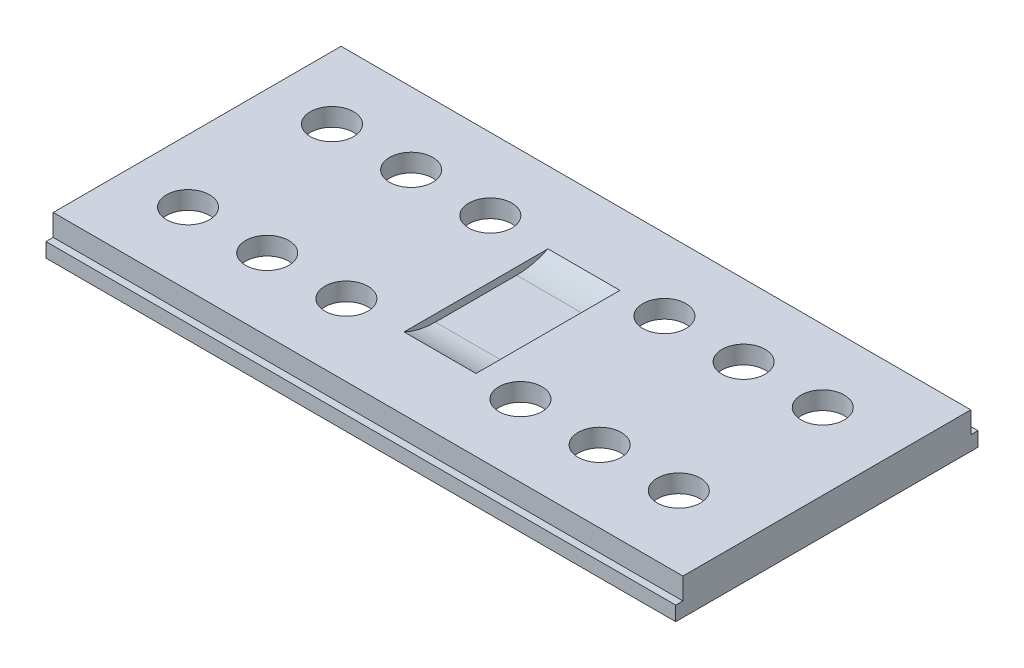
SolidWorks part; units mm, degrees
ref_plane "Front Plane" through (0, 0, 0) normal (0, 0, 1) x (1, 0, 0)
ref_plane "Top Plane" through (0, 0, 0) normal (0, 1, 0) x (1, 0, 0)
ref_plane "Right Plane" through (0, 0, 0) normal (1, 0, 0) x (0, 0, -1)
sketch "Sketch1" plane through (0, 0, 0) normal (0, 1, 0) x (1, 0, 0)
  line L1 (-43.75, 21) -> (43.75, 21)
  line L2 (-43.75, 21) -> (-43.75, -21)
  line L3 (-43.75, -21) -> (43.75, -21)
  line L4 (43.75, 21) -> (43.75, -21)
  line L5 (-43.75, 21) -> (43.75, -21) construction
  line L6 (-43.75, -21) -> (43.75, 21) construction
  point P0 (0, 0)
extrude "Boss-Extrude1" add sketch "Sketch1" along normal blind 5
sketch "Sketch2" plane through (0, 5, 0) normal (0, 1, 0) x (1, 0, 0)
  line L0 (-43.75, 21) -> (-43.75, -21) construction
  line L1 (43.75, 21) -> (-43.75, 21)
  line L2 (43.75, 21) -> (43.75, 20)
  line L3 (43.75, 20) -> (-43.75, 20)
  line L4 (-43.75, 21) -> (-43.75, 20)
  point P7 (0, 0)
extrude "Cut-Extrude1" cut sketch "Sketch2" against normal blind 3
sketch "Sketch3" plane through (0, 5, 0) normal (0, 1, 0) x (1, 0, 0)
  line L0 (43.75, -21) -> (43.75, 20) construction
  line L1 (-43.75, -21) -> (43.75, -21)
  line L2 (-43.75, -21) -> (-43.75, -20)
  line L3 (-43.75, -20) -> (43.75, -20)
  line L4 (43.75, -21) -> (43.75, -20)
extrude "Cut-Extrude2" cut sketch "Sketch3" against normal blind 3
sketch "Sketch4" plane through (0, 5, 0) normal (0, 1, 0) x (1, 0, 0)
  line L1 (-5, 10) -> (5, 10)
  line L2 (-5, 10) -> (-5, -10)
  line L3 (-5, -10) -> (5, -10)
  line L4 (5, 10) -> (5, -10)
  line L5 (-5, 10) -> (5, -10) construction
  line L6 (-5, -10) -> (5, 10) construction
  point P0 (0, 0)
extrude "Cut-Extrude3" cut sketch "Sketch4" against normal blind 1
fillet "Fillet1" radius 10 1 edges at (0, 4, 10)
fillet "Fillet2" radius 10 1 edges at (0, 4, -10)
shell "Shell6" thickness 2.5 removed face at (0, 0, 0)
sketch "Sketch5" plane through (0, 5, 0) normal (0, 1, 0) x (1, 0, 0)
  circle A0 centre (-35.0133, 10) radius 3
  circle A1 centre (-35.0133, -10) radius 3
  circle A2 centre (11.1769, 10) radius 3
  circle A3 centre (11.1769, -10) radius 3
extrude "Cut-Extrude4" cut sketch "Sketch5" against normal blind 2.5
pattern_linear "LPattern1" count 3 spacing 11 along (1, 0, 0) of "Cut-Extrude4"
